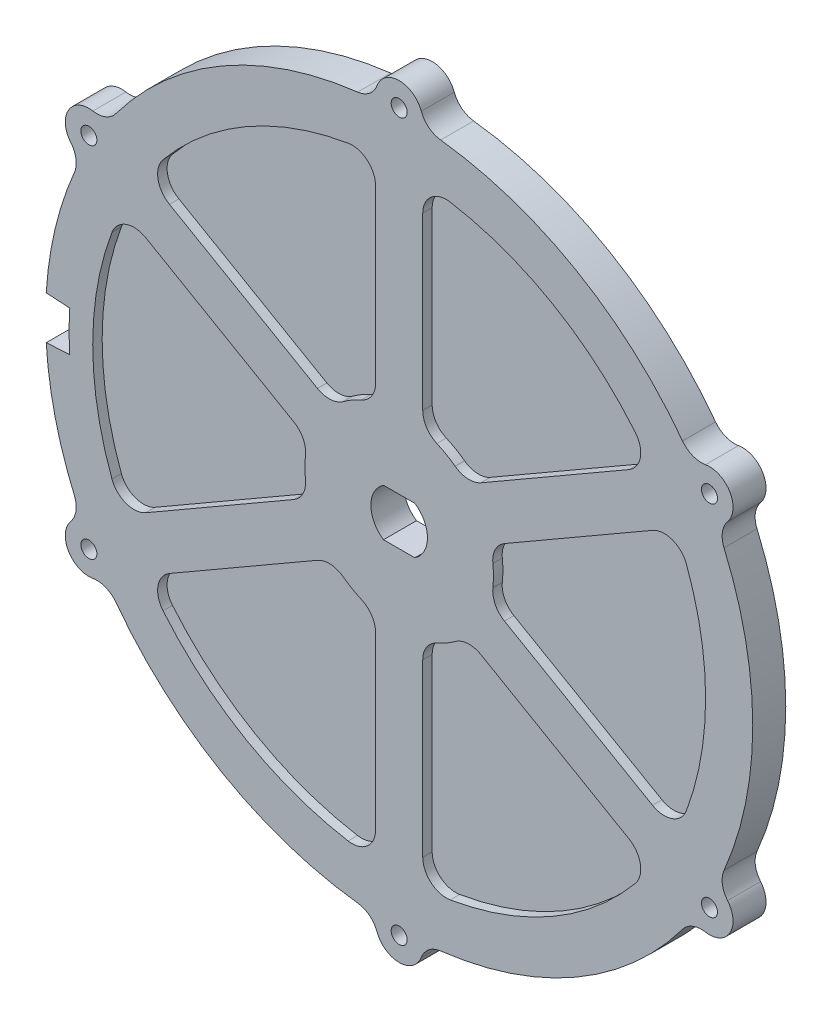
SolidWorks part; units mm, degrees
material "PETG"
ref_plane "Front Plane" through (0, 0, 0) normal (0, 0, 1) x (1, 0, 0)
ref_plane "Top Plane" through (0, 0, 0) normal (0, 1, 0) x (1, 0, 0)
ref_plane "Right Plane" through (0, 0, 0) normal (1, 0, 0) x (0, 0, -1)
sketch "Sketch2" plane through (0, 0, 0) normal (0, 0, 1) x (1, 0, 0)
  line L0 (3.3166, 5) -> (-3.3166, 5)
  line L1 (3.3166, -5) -> (-3.3166, -5)
  circle A0 centre (0, 0) radius 75
  circle A1 centre (0, 0) radius 6
  dimension "D1" = 150
  dimension "D2" = 12
  dimension "D3" = 10
extrude "Boss-Extrude1" add sketch "Sketch2" along normal mid plane 7 contours A0 A1 | L0 A1 | L1 A1 region at (0, 5.403, 0) region at (0, -5.403, 0) region at (-72.8787, 0, 0)
sketch "Sketch4" plane through (0, 0, -3.5) normal (0, 0, 1) x (1, 0, 0)
  line L0 (5, 76) -> (5, 74.8331)
  line L1 (-5, 76) -> (-5, 74.8331)
  arc A0 (5, 76) -> (-5, 76) centre (0, 76) ccw
  circle A1 centre (0, 0) radius 75 construction
  circle A3 centre (0, 0) radius 75
  arc A4 (-5, 74.8331) -> (5, 74.8331) centre (0, 0) ccw
  circle M9 centre (0, 0) radius 75
  dimension "D1" = 5
  dimension "D2" = 76
  dimension "D3" = 0
extrude "Boss-Extrude3" add sketch "Sketch4" along normal up to surface (7 mm away) contours A0 L0 L1 M9 region at (0, 77.5604, -3.5) up to face at (0, 0, 3.5)
fillet "Fillet1" radius 5 2 edges at (-5, 74.8331, 0) (5, 74.8331, 0)
sketch "Sketch6" plane through (0, 0, -3.5) normal (0, 0, -1) x (-1, 0, 0)
  circle A0 centre (0, 76) radius 1.7
  arc A4 (4.6935, 77.7237) -> (-4.6935, 77.7237) centre (0, 76) ccw construction
  dimension "D1" = 3.4
extrude "Cut-Extrude1" cut sketch "Sketch6" against normal through all
pattern_circular "CirPattern1" count 6 over 360 about axis through (0, 0, -3.5) along (0, 0, 1) of "Boss-Extrude3", "Cut-Extrude1", "Fillet1"
sketch "Sketch7" plane through (0, 0, -3.5) normal (0, 0, -1) x (-1, 0, 0)
  line L0 (-5, 59.1608) -> (-5, 22.9129)
  line L1 (5, 59.1608) -> (5, 22.9129)
  line L2 (-5, 19.3649) -> (5, 19.3649) construction
  line L3 (48.7348, 33.9105) -> (17.3431, 15.7866)
  line L4 (53.7348, 25.2503) -> (22.3431, 7.1263)
  line L6 (53.7348, -25.2503) -> (22.3431, -7.1263)
  line L7 (48.7348, -33.9105) -> (17.3431, -15.7866)
  line L9 (5, -59.1608) -> (5, -22.9129)
  line L10 (-5, -59.1608) -> (-5, -22.9129)
  line L12 (-48.7348, -33.9105) -> (-17.3431, -15.7866)
  line L13 (-53.7348, -25.2503) -> (-22.3431, -7.1263)
  line L15 (-53.7348, 25.2503) -> (-22.3431, 7.1263)
  line L16 (-48.7348, 33.9105) -> (-17.3431, 15.7866)
  line L18 (0, 0) -> (8, 18.3303) construction
  line L19 (14.2705, 14.0126) -> (19.2705, 5.3523) construction
  line L20 (19.2705, -5.3523) -> (14.2705, -14.0126) construction
  line L21 (5, -19.3649) -> (-5, -19.3649) construction
  line L22 (-14.2705, -14.0126) -> (-19.2705, -5.3523) construction
  line L23 (-19.2705, 5.3523) -> (-14.2705, 14.0126) construction
  arc A0 (-8, 18.3303) -> (-11.8745, 16.0934) centre (0, 0) ccw
  arc A1 (-10.8333, 64.0909) -> (-50.0876, 41.4274) centre (0, 0) ccw
  arc A2 (5, 22.9129) -> (8, 18.3303) centre (10, 22.9129) ccw
  arc A3 (5, 59.1608) -> (10.8333, 64.0909) centre (10, 59.1608) cw
  arc A4 (-5, 59.1608) -> (-10.8333, 64.0909) centre (-10, 59.1608) ccw
  arc A5 (-5, 22.9129) -> (-8, 18.3303) centre (-10, 22.9129) cw
  arc A6 (22.3431, 7.1263) -> (19.8745, 2.2369) centre (24.8431, 2.7962) ccw
  arc A7 (53.7348, 25.2503) -> (60.921, 22.6635) centre (56.2348, 20.9201) cw
  arc A8 (48.7348, 33.9105) -> (50.0876, 41.4274) centre (46.2348, 38.2407) ccw
  arc A9 (17.3431, 15.7866) -> (11.8745, 16.0934) centre (14.8431, 20.1167) cw
  arc A10 (17.3431, -15.7866) -> (11.8745, -16.0934) centre (14.8431, -20.1167) ccw
  arc A11 (48.7348, -33.9105) -> (50.0876, -41.4274) centre (46.2348, -38.2407) cw
  arc A12 (53.7348, -25.2503) -> (60.921, -22.6635) centre (56.2348, -20.9201) ccw
  arc A13 (22.3431, -7.1263) -> (19.8745, -2.2369) centre (24.8431, -2.7962) cw
  arc A14 (-5, -22.9129) -> (-8, -18.3303) centre (-10, -22.9129) ccw
  arc A15 (-5, -59.1608) -> (-10.8333, -64.0909) centre (-10, -59.1608) cw
  arc A16 (5, -59.1608) -> (10.8333, -64.0909) centre (10, -59.1608) ccw
  arc A17 (5, -22.9129) -> (8, -18.3303) centre (10, -22.9129) cw
  arc A18 (-22.3431, -7.1263) -> (-19.8745, -2.2369) centre (-24.8431, -2.7962) ccw
  arc A19 (-53.7348, -25.2503) -> (-60.921, -22.6635) centre (-56.2348, -20.9201) cw
  arc A20 (-48.7348, -33.9105) -> (-50.0876, -41.4274) centre (-46.2348, -38.2407) ccw
  arc A21 (-17.3431, -15.7866) -> (-11.8745, -16.0934) centre (-14.8431, -20.1167) cw
  arc A22 (-17.3431, 15.7866) -> (-11.8745, 16.0934) centre (-14.8431, 20.1167) ccw
  arc A23 (-48.7348, 33.9105) -> (-50.0876, 41.4274) centre (-46.2348, 38.2407) cw
  arc A24 (-53.7348, 25.2503) -> (-60.921, 22.6635) centre (-56.2348, 20.9201) ccw
  arc A25 (-22.3431, 7.1263) -> (-19.8745, 2.2369) centre (-24.8431, 2.7962) cw
  arc A26 (11.8745, 16.0934) -> (8, 18.3303) centre (0, 0) ccw
  arc A27 (19.8745, -2.2369) -> (19.8745, 2.2369) centre (0, 0) ccw
  arc A28 (8, -18.3303) -> (11.8745, -16.0934) centre (0, 0) ccw
  arc A29 (-11.8745, -16.0934) -> (-8, -18.3303) centre (0, 0) ccw
  arc A30 (-19.8745, 2.2369) -> (-19.8745, -2.2369) centre (0, 0) ccw
  arc A31 (50.0876, 41.4274) -> (10.8333, 64.0909) centre (0, 0) ccw
  arc A32 (60.921, -22.6635) -> (60.921, 22.6635) centre (0, 0) ccw
  arc A33 (10.8333, -64.0909) -> (50.0876, -41.4274) centre (0, 0) ccw
  arc A34 (-50.0876, -41.4274) -> (-10.8333, -64.0909) centre (0, 0) ccw
  arc A35 (-60.921, 22.6635) -> (-60.921, -22.6635) centre (0, 0) ccw
  point P8 (0, 19.3649)
  dimension "D1" = 130
  dimension "D2" = 40
  dimension "D4" = 5
  dimension "D3" = 10
  dimension "D5" = 6
extrude "Cut-Extrude2" cut sketch "Sketch7" against normal blind 2
mirror "Mirror1" about plane through (0, 0, 0) normal (0, 0, 1) of "Cut-Extrude2"
sketch "Sketch9" plane through (0, 0, 0) normal (0, 1, 0) x (1, 0, 0)
  line L0 (-8.8003, 3.5) -> (-60.1031, 3.5) construction
  line L1 (-75, -3.5) -> (-70, -3.5)
  line L2 (-75, -3.5) -> (-75, 3.5)
  line L3 (-75, 3.5) -> (-70, 3.5)
  line L4 (-70, -3.5) -> (-70, 3.5)
  line L5 (-60.1031, -3.5) -> (-8.8003, -3.5) construction
  line L6 (0, 0) -> (0, 49.8627) construction
  line L7 (-68.9034, 3.5) -> (-75, 3.5) construction
  line L8 (-75, 3.5) -> (-75, -3.5) construction
  dimension "D1" = 5
revolve "Cut-Revolve1" cut sketch "Sketch9" angle 7 mid plane about L6
